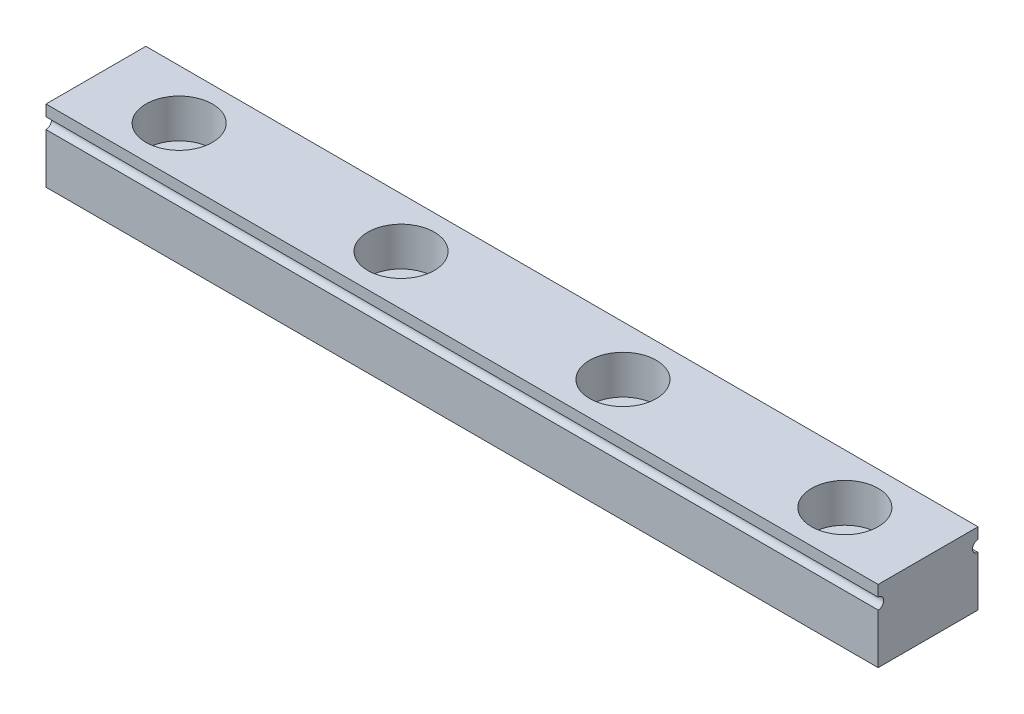
SolidWorks part; units mm, degrees
material "Plain Carbon Steel"
ref_plane "Front Plane" through (0, 0, 0) normal (0, 0, 1) x (1, 0, 0)
ref_plane "Top Plane" through (0, 0, 0) normal (0, 1, 0) x (1, 0, 0)
ref_plane "Right Plane" through (0, 0, 0) normal (1, 0, 0) x (0, 0, -1)
sketch "Sketch1" plane through (0, 0, 0) normal (1, 0, 0) x (0, 0, -1)
  line L1 (-4.5, 3.25) -> (4.5, 3.25)
  line L2 (-4.5, 3.25) -> (-4.5, -3.25)
  line L3 (-4.5, -3.25) -> (4.5, -3.25)
  line L4 (4.5, 3.25) -> (4.5, -3.25)
  line L5 (-4.5, 3.25) -> (4.5, -3.25) construction
  line L6 (-4.5, -3.25) -> (4.5, 3.25) construction
  circle A0 centre (-4.5, 1.75) radius 0.5
  circle A1 centre (4.5, 1.75) radius 0.5
  point P0 (0, 0)
  dimension "D3" = 1
  dimension "D4" = 1.5
  dimension "D1" = 6.5
  dimension "D2" = 9
extrude "it is 6.5mm, dont fuckin change" add sketch "Sketch1" along normal blind 75 contours A1 L4 L1 L2 A0 L3 region at (0, -0.0238, 0)
sketch "Sketch2" plane through (0, 3.25, 0) normal (0, 1, 0) x (1, 0, 0)
  line L1 (27.5, 0) -> (37.5, 4.5) construction
  line L2 (75, 4.5) -> (0, 4.5) construction
  line L3 (37.5, 4.5) -> (47.5, 0) construction
  circle A0 centre (7.5, 0) radius 1.5
  circle A1 centre (27.5, 0) radius 1.5
  circle A2 centre (47.5, 0) radius 1.5
  circle A3 centre (67.5, 0) radius 1.5
  dimension "D2" = 3
  dimension "D4" = 20
  dimension "D3" = 4
extrude "Cut-Extrude1" cut sketch "Sketch2" against normal through all
sketch "Sketch3" plane through (0, 3.25, 0) normal (0, 1, 0) x (1, 0, 0)
  circle A0 centre (7.5, 0) radius 3
  circle A1 centre (27.5, 0) radius 3
  circle A2 centre (47.5, 0) radius 3
  circle A15 centre (67.5, 0) radius 3
  dimension "D1" = 6
  dimension "D3" = 20
  dimension "D2" = 4
extrude "Cut-Extrude2" cut sketch "Sketch3" against normal blind 3.5
equation "\"l\" = 75'length(7.5*2+20*n) n is an interger"
equation "\"D1@it is 6.5mm, dont fuckin change\" = \"l\""
equation "\"D2@Sketch3\"=(\"l\"-15)/20+1"
equation "\"D3@Sketch2\"=(\"l\"-15)/20+1"
